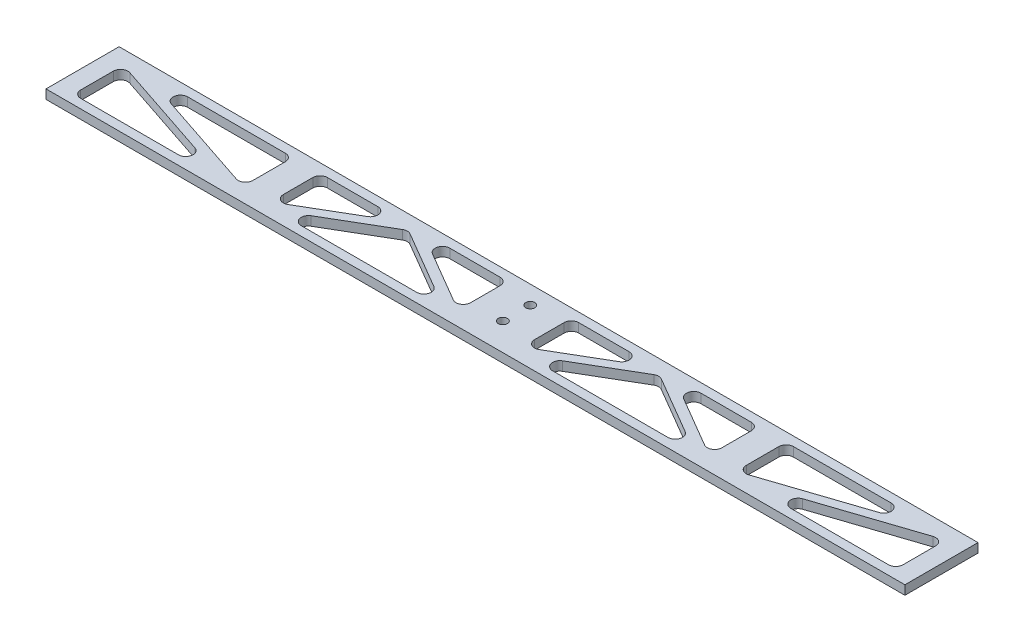
SolidWorks part; units mm, degrees
material "Balsa"
ref_plane "Front Plane" through (0, 0, 0) normal (0, 0, 1) x (1, 0, 0)
ref_plane "Top Plane" through (0, 0, 0) normal (0, 1, 0) x (1, 0, 0)
ref_plane "Right Plane" through (0, 0, 0) normal (1, 0, 0) x (0, 0, -1)
sketch "Sketch1" plane through (0, 0, 0) normal (0, 1, 0) x (1, 0, 0)
  line L1 (149.225, -12.7) -> (-149.225, -12.7)
  line L2 (149.225, -12.7) -> (149.225, 12.7)
  line L3 (149.225, 12.7) -> (-149.225, 12.7)
  line L4 (-149.225, -12.7) -> (-149.225, 12.7)
  point P0 (0, 12.7)
  point P6 (-149.225, 0)
  dimension "D1" = 25.4
  dimension "D2" = 298.45
extrude "Boss-Extrude1" add sketch "Sketch1" along normal blind 3.175
sketch "Sketch2" plane through (0, 3.175, 0) normal (0, 1, 0) x (1, 0, 0)
  line L0 (149.225, -12.7) -> (149.225, 12.7) construction
  line L2 (-149.225, 12.7) -> (-149.225, -12.7) construction
  line L4 (149.225, -12.7) -> (149.225, 12.7)
  line L6 (-149.225, 12.7) -> (-149.225, -12.7)
  line L8 (149.225, 9.525) -> (-149.225, 9.525)
  line L9 (-149.225, -9.525) -> (149.225, -9.525)
  line L10 (-142.875, 9.525) -> (-142.875, -9.525)
  line L11 (-80.9625, 9.525) -> (-80.9625, -9.525) construction
  line L12 (142.875, 9.525) -> (142.875, -9.525)
  line L13 (0, -9.525) -> (0, 9.525) construction
  line L14 (11.1125, 9.525) -> (11.1125, -9.525)
  line L15 (-11.1125, 9.525) -> (-11.1125, -9.525)
  line L16 (-85.725, 9.525) -> (-85.725, -9.525)
  line L17 (-76.2, 9.525) -> (-76.2, -9.525)
  line L18 (80.9625, 9.525) -> (80.9625, -9.525) construction
  line L19 (85.725, 9.525) -> (85.725, -9.525)
  line L20 (76.2, 9.525) -> (76.2, -9.525)
  line L21 (-76.2, -9.525) -> (-43.6562, 9.525)
  line L22 (-43.6562, 9.525) -> (-11.1125, -9.525)
  line L23 (-85.725, -9.525) -> (-142.875, 9.525)
  line L24 (11.1125, -9.525) -> (43.6562, 9.525)
  line L25 (43.6562, 9.525) -> (76.2, -9.525)
  line L26 (85.725, -9.525) -> (142.875, 9.525)
  line L27 (-85.223, -8.019) -> (-142.373, 11.031)
  line L28 (-75.398, -10.895) -> (-43.6562, 7.6855)
  line L29 (-43.6562, 7.6855) -> (-11.9145, -10.895)
  line L30 (11.9145, -10.895) -> (43.6562, 7.6855)
  line L31 (43.6562, 7.6855) -> (75.398, -10.895)
  line L32 (86.227, -11.031) -> (143.377, 8.019)
  line L33 (-86.227, -11.031) -> (-143.377, 8.019)
  line L34 (-77.002, -8.155) -> (-43.6562, 11.3645)
  line L35 (-43.6562, 11.3645) -> (-10.3105, -8.155)
  line L36 (10.3105, -8.155) -> (43.6562, 11.3645)
  line L37 (43.6562, 11.3645) -> (77.002, -8.155)
  line L38 (85.223, -8.019) -> (142.373, 11.031)
  dimension "D1" = 3.175
  dimension "D2" = 3.175
  dimension "D3" = 6.35
  dimension "D4" = 6.35
  dimension "D11" = 4.7625
  dimension "D12" = 4.7625
  dimension "D8" = 9.525
  dimension "D9" = 4.7625
  dimension "D7" = 63.5
  dimension "D10" = 63.5
  dimension "D5" = 22.225
  dimension "D6" = 11.1125
  dimension "D13" = 1.5875
  dimension "D14" = 1.5875
extrude "Cut-Extrude1" cut sketch "Sketch2" against normal through all contours L9 L33 L10 | L27 L16 L8 | L17 L34 L8 | L29 L28 L9 | L8 L35 L15 | L14 L36 L8 | L31 L30 L9 | L8 L37 L20 | L19 L38 L8 | L32 L9 L12 region at (125.4984, 3.175, 3.7328) region at (103.1016, 3.175, -3.7328) region at (66.3996, 3.175, -3.7882) region at (43.6562, 3.175, 3.7882) region at (20.9129, 3.175, -3.7882) region at (-20.9129, 3.175, -3.7882) region at (-43.6562, 3.175, 3.7882) region at (-66.3996, 3.175, -3.7882) region at (-103.1016, 3.175, -3.7328) region at (-125.4984, 3.175, 3.7328)
sketch "Sketch3" plane through (0, 3.175, 0) normal (0, 1, 0) x (1, 0, 0)
  circle A0 centre (0, 6.35) radius 1.5875
  circle A1 centre (0, -3.175) radius 1.5875
  dimension "D1" = 3.175
  dimension "D2" = 9.525
  dimension "D3" = 6.35
extrude "Cut-Extrude2" cut sketch "Sketch3" against normal through all
fillet "Fillet1" radius 2.54 30 edges at (-14.2549, 1.5875, 9.525) (-73.0576, 1.5875, 9.525) (-43.6562, 1.5875, -7.6855) (-11.1125, 1.5875, 7.6855) (-40.5138, 1.5875, -9.525) (-11.1125, 1.5875, -9.525) (-46.7987, 1.5875, -9.525) (-76.2, 1.5875, 7.6855) (-76.2, 1.5875, -9.525) (73.0576, 1.5875, 9.525) (14.2549, 1.5875, 9.525) (43.6562, 1.5875, -7.6855) (142.875, 1.5875, -7.8516) (142.875, 1.5875, 9.525) (90.7451, 1.5875, 9.525) (40.5138, 1.5875, -9.525) (11.1125, 1.5875, 7.6855) (11.1125, 1.5875, -9.525) (76.2, 1.5875, 7.6855) (46.7987, 1.5875, -9.525) (76.2, 1.5875, -9.525) (137.8549, 1.5875, -9.525) (85.725, 1.5875, 7.8516) (85.725, 1.5875, -9.525) (-137.8549, 1.5875, -9.525) (-85.725, 1.5875, 7.8516) (-85.725, 1.5875, -9.525) (-90.7451, 1.5875, 9.525) (-142.875, 1.5875, 9.525) (-142.875, 1.5875, -7.8516)
move or copy body "Body-Move/Copy1" [suppressed] bodies to move or copy 103 parameters "D1"=0, "D2"=0, "D3"=0
equation "\"D10@Sketch2\"=\"D7@Sketch2\""
equation "\"D6@Sketch2\"=\"D5@Sketch2\"/2"
